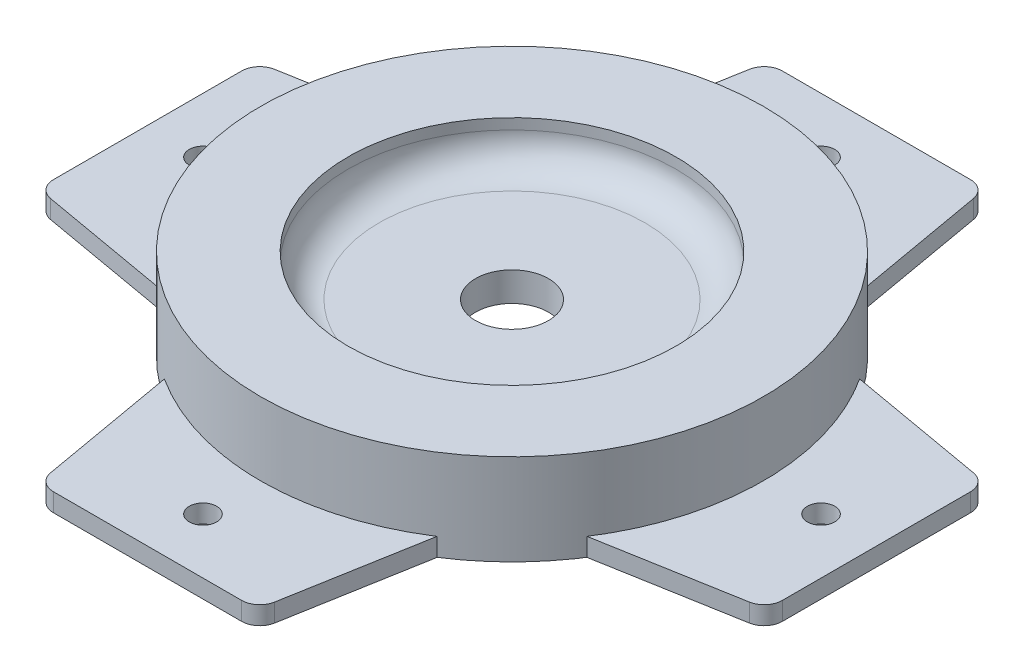
SolidWorks part; units mm, degrees
material "AISI 1020"
ref_plane "Front Plane" through (0, 0, 0) normal (0, 0, 1) x (1, 0, 0)
ref_plane "Top Plane" through (0, 0, 0) normal (0, 1, 0) x (1, 0, 0)
ref_plane "Right Plane" through (0, 0, 0) normal (1, 0, 0) x (0, 0, -1)
sketch "Sketch1" plane through (0, 0, 0) normal (0, 0, 1) x (1, 0, 0)
  line L0 (0, 92.5968) -> (0, -53.0582) construction
  line L2 (87.63, -7.0866) -> (87.63, 24.6634)
  line L4 (87.63, 24.6634) -> (57.15, 24.6634)
  line L7 (57.15, 24.6634) -> (57.15, 10.16)
  line L8 (57.15, 10.16) -> (0, 10.16)
  line L9 (0, 10.16) -> (0, 0)
  line L10 (0, 0) -> (57.15, 0)
  line L11 (57.15, 0) -> (57.15, -7.0866)
  line L12 (57.15, -7.0866) -> (87.63, -7.0866)
  point P9 (0, 0)
  dimension "D1" = 57.15
  dimension "D2" = 87.63
  dimension "D3" = 57.15
  dimension "D4" = 7.0866
  dimension "D5" = 10.16
  dimension "D7" = 31.75
revolve "Revolve1" add sketch "Sketch1" angle 360 about L0
hole_wizard "1 (1) Diameter Hole1" positions "Sketch7" profile "Sketch9" hole size "1" standard "ANSI Inch" end condition through all
sketch "Sketch7" plane through (0, 10.16, 0) normal (0, 1, 0) x (1, 0, 0)
  point P0 (0, 0)
sketch "Sketch9" plane through (0, 10.16, 0) normal (1, 0, 0) x (0, 0, 1)
  line L0 (0, 0) -> (0, 17.2466)
  line L1 (0, 17.2466) -> (12.7, 17.2466)
  line L2 (12.7, 17.2466) -> (12.7, 0)
  line L5 (12.7, 0) -> (0, 0)
  line L11 (0, -6.35) -> (0, 107.95) construction
  dimension "Thru Hole Dia." = 25.4
  dimension "Thru Hole Depth" = 17.2466
sketch "Sketch14" plane through (0, 10.16, 0) normal (0, -1, 0) x (1, 0, 0)
  circle A0 centre (0, 0) radius 19.05
  dimension "D1" = 38.1
sketch "Sketch15" plane through (0, -7.0866, 0) normal (0, -1, 0) x (1, 0, 0)
  line L4 (0, 0) -> (-157.4172, 0) construction
  line L6 (-127, -38.1) -> (-73.633, -47.51)
  line L9 (-127, 38.1) -> (-127, -38.1)
  line L10 (0, -55) -> (0, 55) construction
  line L11 (-127, 38.1) -> (-73.633, 47.51)
  circle A0 centre (0, 0) radius 87.63 construction
  arc A1 (-73.633, 47.51) -> (-73.633, -47.51) centre (0, 0) ccw
  dimension "D1" = 76.2
  dimension "D4" = 127
  dimension "D5" = 100
extrude "Boss-Extrude1" add sketch "Sketch15" against normal blind 6.35 separate body
fillet "Fillet2" radius 6.35 2 edges at (-127, -3.9116, -38.1) (-127, -3.9116, 38.1)
hole_wizard "3/8 (0.375) Diameter Hole1" positions "Sketch16" profile "Sketch17" hole size "3/8" standard "ANSI Inch"
sketch "Sketch16" plane through (0, -0.7366, 0) normal (0, 1, 0) x (1, 0, 0)
  point P0 (-107.696, 0)
  dimension "D1" = 107.696
sketch "Sketch17" plane through (-107.696, -0.7366, 0) normal (1, 0, 0) x (0, 0, 1)
  line L0 (0, 0) -> (0, 28.2616)
  line L1 (0, 28.2616) -> (4.7625, 25.4)
  line L2 (4.7625, 25.4) -> (4.7625, 0)
  line L5 (4.7625, 0) -> (0, 0)
  line L10 (0, 28.2616) -> (-4.7625, 25.4) construction
  line L11 (0, -6.35) -> (0, 107.95) construction
  dimension "Hole Dia." = 9.525
  dimension "Hole Depth" = 25.4
  dimension "Drill Angle" = 118
pattern_circular "CirPattern4" count 4 over 360 about axis through (0, 24.6634, 0) along (0, 1, 0) of bodies 121
fillet "Fillet3" radius 10.795 2 edges at (0, 0, 57.15) (0, 10.16, 57.15)
